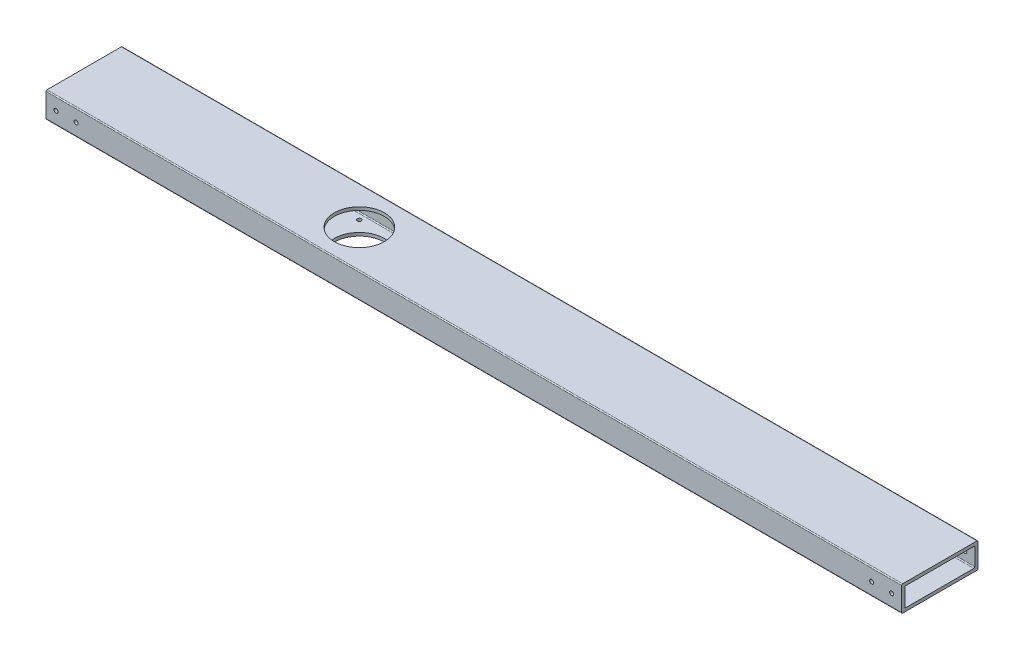
SolidWorks part; units mm, degrees
ref_plane "Front Plane" through (0, 0, 0) normal (0, 0, 1) x (1, 0, 0)
ref_plane "Top Plane" through (0, 0, 0) normal (0, 1, 0) x (1, 0, 0)
ref_plane "Right Plane" through (0, 0, 0) normal (1, 0, 0) x (0, 0, -1)
sketch "Sketch1" plane through (0, 0, 0) normal (1, 0, 0) x (0, 0, -1)
  line L1 (38.1, -12.7) -> (-38.1, -12.7)
  line L2 (38.1, -12.7) -> (38.1, 12.7)
  line L3 (38.1, 12.7) -> (-38.1, 12.7)
  line L4 (-38.1, -12.7) -> (-38.1, 12.7)
  line L5 (38.1, -12.7) -> (-38.1, 12.7) construction
  line L6 (38.1, 12.7) -> (-38.1, -12.7) construction
  line L7 (34.925, -9.525) -> (-34.925, -9.525)
  line L8 (34.925, -9.525) -> (34.925, 9.525)
  line L9 (34.925, 9.525) -> (-34.925, 9.525)
  line L10 (-34.925, -9.525) -> (-34.925, 9.525)
  line L11 (34.925, -9.525) -> (-34.925, 9.525) construction
  line L12 (34.925, 9.525) -> (-34.925, -9.525) construction
  point P0 (0, 0)
  point P6 (0, 0)
  point P11 (-8.1058, 8.1058)
  dimension "D1" = 76.2
  dimension "D2" = 25.4
  dimension "D3" = 3.175
  dimension "D4" = 3.175
extrude "Boss-Extrude1" add sketch "Sketch1" along normal mid plane 854.4
fillet "Fillet1" radius 1 8 edges at (0, -12.7, -38.1) (0, 9.525, -34.925) (0, -9.525, 34.925) (0, 9.525, 34.925) (0, -12.7, 38.1) (0, -9.525, -34.925) (0, 12.7, -38.1) (0, 12.7, 38.1)
sketch "Sketch2" plane through (0, 12.7, 0) normal (0, 1, 0) x (1, 0, 0)
  line L0 (-427.2, 37.1) -> (-427.2, -37.1) construction
  circle A0 centre (-152.4, 0) radius 25
  point P3 (0, 0)
  point P4 (-97.9443, 4.1796)
  point P6 (0, 0)
  dimension "D1" = 50
  dimension "D2" = 274.8
extrude "Cut-Extrude1" cut sketch "Sketch2" against normal through all
sketch "Sketch3" plane through (0, 12.7, 0) normal (0, 1, 0) x (1, 0, 0)
  line L1 (-197.2494, -25.5518) -> (-243.937, -25.5518)
  line L2 (-197.2494, -25.5518) -> (-197.2494, 25.5518)
  line L3 (-197.2494, 25.5518) -> (-243.937, 25.5518)
  line L4 (-243.937, -25.5518) -> (-243.937, 25.5518)
  line L5 (-197.2494, -25.5518) -> (-243.937, 25.5518) construction
  line L6 (-197.2494, 25.5518) -> (-243.937, -25.5518) construction
  point P0 (-220.5932, 0)
split line "Split Line1" [suppressed]
sketch "Sketch4" plane through (0, 0, 38.1) normal (0, 0, 1) x (1, 0, 0)
  line L0 (-427.2, 11.7) -> (-427.2, -11.7) construction
  point P0 (-417.2, 0)
  point P2 (-397.2, 0)
  point P7 (0, 0)
  dimension "D1" = 20
  dimension "D2" = 10
hole_wizard "Ø4.0mm Dowel Hole1" positions "Sketch4" profile "Sketch5" hole size "Ø4.0" standard "ANSI Metric" end condition through all
sketch "Sketch5" plane through (-417.2, 0, 38.1) normal (1, 0, 0) x (0, -1, 0)
  line L0 (0, 0) -> (0, 76.2)
  line L1 (0, 76.2) -> (2, 76.2)
  line L2 (2, 76.2) -> (2, 0)
  line L5 (2, 0) -> (0, 0)
  line L11 (0, -6.35) -> (0, 107.95) construction
  dimension "Thru Hole Dia." = 4
  dimension "Thru Hole Depth" = 76.2
mirror "Mirror1" about plane through (0, 0, 0) normal (1, 0, 0) of "Ø4.0mm Dowel Hole1"
hole_wizard "Ø4.0mm Dowel Hole2" positions "Sketch6" profile "Sketch7" hole size "Ø4.0" standard "ANSI Metric" end condition up to next
sketch "Sketch6" plane through (0, -12.7, 0) normal (0, -1, 0) x (-1, 0, 0)
  line L0 (123.8329, -28.5671) -> (180.9671, -28.5671) construction
  line L1 (180.9671, -28.5671) -> (180.9671, 28.5671) construction
  line L2 (180.9671, 28.5671) -> (123.8329, 28.5671) construction
  line L3 (123.8329, 28.5671) -> (123.8329, -28.5671) construction
  circle A1 centre (152.4, 0) radius 25.4 construction
  circle A2 centre (152.4, 0) radius 40.4 construction
  point P1 (180.9671, -28.5671)
  point P3 (180.9671, 28.5671)
  point P5 (123.8329, 28.5671)
  point P7 (123.8329, -28.5671)
  point P21 (123.8329, 0)
  point P203 (152.4, 28.5671)
  dimension "D1" = 50.8
  dimension "D2" = 15
sketch "Sketch7" plane through (-180.9671, -12.7, 28.5671) normal (1, 0, 0) x (0, 0, -1)
  line L0 (0, 0) -> (0, 3.175)
  line L1 (0, 3.175) -> (2, 3.175)
  line L2 (2, 3.175) -> (2, 0)
  line L5 (2, 0) -> (0, 0)
  line L11 (0, -6.35) -> (0, 107.95) construction
  dimension "Thru Hole Dia." = 4
  dimension "Thru Hole Depth" = 3.175
